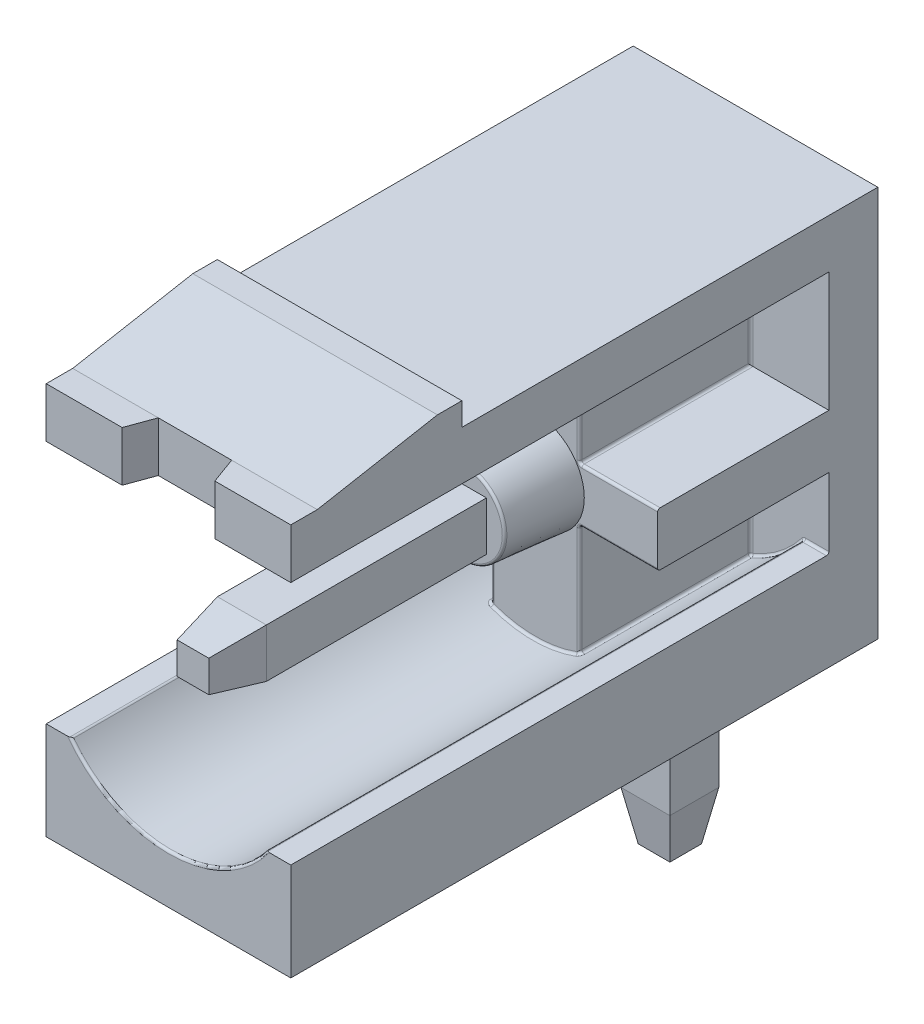
SolidWorks part; units mm, degrees
ref_plane "Спереди" through (0, 0, 0) normal (0, 0, 1) x (1, 0, 0)
ref_plane "Сверху" through (0, 0, 0) normal (0, 1, 0) x (1, 0, 0)
ref_plane "Справа" through (0, 0, 0) normal (1, 0, 0) x (0, 0, -1)
sketch "Эскиз1" plane through (0, 0, 0) normal (0, 0, 1) x (1, 0, 0)
  line L1 (-2.5, 0) -> (2.5, 0)
  line L2 (-2.5, 0) -> (-2.5, 8)
  line L3 (-2.5, 8) -> (2.5, 8)
  line L4 (2.5, 0) -> (2.5, 8)
extrude "Вытянуть1" add sketch "Эскиз1" along normal blind 12
sketch "Эскиз2" plane through (0, 0, 12) normal (0, 0, 1) x (1, 0, 0)
  line L0 (-2.5, 8) -> (-2.5, 0) construction
  line L1 (-2.5, 7) -> (2.5, 7)
  line L2 (-2.5, 7) -> (-2.5, 2)
  line L3 (-2.5, 2) -> (2.5, 2)
  line L4 (2.5, 7) -> (2.5, 2)
  line L5 (2.5, 0) -> (2.5, 8) construction
  dimension "D1" = 1
  dimension "D2" = 2
extrude "Вытянуть2" cut sketch "Эскиз2" against normal blind 11
sketch "Эскиз5" plane through (0, 0, 12) normal (0, 0, 1) x (1, 0, 0)
  line L0 (-2.5, 2) -> (-2, 2) construction
  line L1 (-2.5, 2) -> (2.5, 2) construction
  line L2 (2.5, 2) -> (2, 2) construction
  line L3 (0, 0) -> (0, 1) construction
  line L4 (-2.5, 0) -> (2.5, 0) construction
  circle A0 centre (0, 3.5) radius 2.5
extrude "Вытянуть3" cut sketch "Эскиз5" against normal blind 11
sketch "Эскиз6" plane through (0, 0, 12) normal (0, 0, 1) x (1, 0, 0)
  line L1 (0.5, 4.5) -> (-0.5, 4.5)
  line L2 (0.5, 4.5) -> (0.5, 3.5)
  line L3 (0.5, 3.5) -> (-0.5, 3.5)
  line L4 (-0.5, 4.5) -> (-0.5, 3.5)
  line L5 (0.5, 4.5) -> (-0.5, 3.5) construction
  line L6 (0.5, 3.5) -> (-0.5, 4.5) construction
  point P0 (0, 4)
  dimension "D1" = 1
  dimension "D2" = 1
sketch "Эскиз9" plane through (0, 0, 0) normal (0, -1, 0) x (1, 0, 0)
  line L0 (-2.5, 1.75) -> (2.5, 1.75) construction
  line L1 (-2.5, 12) -> (-2.5, 0) construction
  line L2 (2.5, 12) -> (2.5, 0) construction
  line L4 (-0.5, 2.25) -> (0.5, 2.25)
  line L5 (-0.5, 2.25) -> (-0.5, 1.25)
  line L6 (-0.5, 1.25) -> (0.5, 1.25)
  line L7 (0.5, 2.25) -> (0.5, 1.25)
  line L8 (-0.5, 2.25) -> (0.5, 1.25) construction
  line L9 (-0.5, 1.25) -> (0.5, 2.25) construction
  point P2 (0, 1.75)
  dimension "D1" = 1.75
sketch "Эскиз13" plane through (0, 0, 1) normal (0, 0, 1) x (1, 0, 0)
  line L0 (2.5, 7) -> (-2.5, 7) construction
  line L1 (-0.9, 1) -> (0.9, 1)
  line L2 (-0.9, 1) -> (-0.9, 7)
  line L3 (-0.9, 7) -> (0.9, 7)
  line L4 (0.9, 1) -> (0.9, 7)
  line L5 (-0.9, 1) -> (0.9, 7) construction
  line L6 (-0.9, 7) -> (0.9, 1) construction
  line L7 (2.5, 2) -> (2.5, 7) construction
  line L8 (-2.5, 4.55) -> (2.5, 4.55)
  line L9 (-2.5, 4.55) -> (-2.5, 3.45)
  line L10 (-2.5, 3.45) -> (2.5, 3.45)
  line L11 (2.5, 4.55) -> (2.5, 3.45)
  line L12 (-2.5, 4.55) -> (2.5, 3.45) construction
  line L13 (-2.5, 3.45) -> (2.5, 4.55) construction
  point P0 (0, 4)
  point P7 (0, 4)
  line M1 (2.5, 2) -> (2.5, 7)
  line M2 (2.5, 7) -> (-2.5, 7)
  line M3 (-2.5, 7) -> (-2.5, 2)
  arc M5 (-2, 2) -> (2, 2) centre (0, 3.5) ccw
  dimension "D1" = 1.1
  dimension "D2" = 1.8
extrude "Вытянуть13" add sketch "Эскиз13" along normal blind 3.5 contours L2 L10 L4 L8 | L2 L8 L4 M2 | L10 L2 L8 M3 | L10 L2 L4 M5 | L4 L10 L8 M1 region at (0, 2.252, 1) region at (-1.7, 4, 1) region at (0, 4, 1) region at (1.7, 4, 1) region at (0, 5.775, 1)
sketch "Эскиз14" plane through (0, 0, 4.5) normal (0, 0, 1) x (1, 0, 0)
  circle A0 centre (0, 4) radius 1
extrude "Вытянуть14" add sketch "Эскиз14" along normal blind 1.5
chamfer "Фаска1" distance 1.5 angle 5 1 edges at (1, 4, 6) first distance on face at (1, 4, 6)
sketch "Эскиз15" plane through (2.5, 0, 0) normal (1, 0, 0) x (0, 0, -1)
  line L0 (-12, 8) -> (-8.5024, 8)
  line L1 (-12, 8) -> (0, 8) construction
  line L2 (-8.5024, 8) -> (-8.5024, 8.4712)
  line L3 (-8.5024, 8.4712) -> (-9.0026, 8.4712)
  line L4 (-9.0026, 8.4712) -> (-11.4588, 8.0219)
  line L5 (-11.4588, 8.0219) -> (-12, 8.0219)
  line L6 (-12, 8.0219) -> (-12, 8)
extrude "Вытянуть15" add sketch "Эскиз15" against normal blind 5
sketch "Эскиз16" plane through (0, 8.0219, 0) normal (0, 1, 0) x (1, 0, 0)
  line L0 (0.75, -11.4588) -> (-0.75, -11.4588)
  line L1 (-2.5, -11.4588) -> (2.5, -11.4588) construction
  line L2 (-0.75, -11.4588) -> (-0.947, -12)
  line L3 (-2.5, -12) -> (2.5, -12) construction
  line L4 (0.75, -11.4588) -> (0.947, -12)
  line L5 (0.947, -12) -> (-0.947, -12)
  dimension "D1" = 1.75
  dimension "D2" = 1.75
extrude "Вытянуть16" cut sketch "Эскиз16" against normal up to next
sketch "Эскиз17" plane through (0, 0, 0) normal (0, 0, -1) x (-1, 0, 0)
  line L0 (2.5, 0) -> (-2.5, 0) construction
  line L1 (-0.6, 0) -> (0.6, 0)
  line L2 (-0.6, 0) -> (-0.6, 5)
  line L3 (-0.6, 5) -> (0.6, 5)
  line L4 (0.6, 0) -> (0.6, 5)
  dimension "D1" = 3
  dimension "D2" = 1.2
  dimension "D3" = 1.9
extrude "Вытянуть17" cut sketch "Эскиз17" against normal blind 2.25
sketch "Эскиз18" plane through (0, 0, 0) normal (0, 0, -1) x (-1, 0, 0)
  line L0 (-0.6, 0) -> (-2.5, 0) construction
  line L1 (-1.75, 0) -> (1.75, 0)
  line L2 (-1.75, 0) -> (-1.75, 6)
  line L3 (-1.75, 6) -> (1.75, 6)
  line L4 (1.75, 0) -> (1.75, 6)
  dimension "D1" = 0.75
  dimension "D2" = 3.5
  dimension "D3" = 2
extrude "Вытянуть18" cut sketch "Эскиз18" against normal blind 0.1
extrude "Вытянуть19" add sketch "Эскиз6" against normal up to body separate body
sketch "Эскиз19" plane through (0, 0, 12) normal (0, 0, 1) x (1, 0, 0)
  line L1 (-0.5, 4.5) -> (0.5, 4.5)
  line L2 (-0.5, 4.5) -> (-0.5, 3.5)
  line L3 (-0.5, 3.5) -> (0.5, 3.5)
  line L4 (0.5, 4.5) -> (0.5, 3.5)
extrude "Вытянуть20" cut sketch "Эскиз19" against normal blind 0.5
extrude "Вытянуть22" add sketch "Эскиз9" against normal up to body and the other way blind 4 separate body
chamfer "Фаска2" distance 1 angle 10 4 edges at (0, 4.5, 11.5) (0.5, 4, 11.5) (0, 3.5, 11.5) (-0.5, 4, 11.5) first distance on face at (0, 4.5, 8.75) first distance on face at (0.5, 4, 8.75) first distance on face at (0, 3.5, 8.75) first distance on face at (-0.5, 4, 8.75)
chamfer "Фаска3" distance 1 angle 10 4 edges at (0, -4, 1.25) (-0.5, -4, 1.75) (0, -4, 2.25) (0.5, -4, 1.75) first distance on face at (0, 0.5, 1.25) first distance on face at (-0.5, 0.5, 1.75) first distance on face at (0, 0.5, 2.25) first distance on face at (0.5, 0.5, 1.75)
fillet "Скругление3" radius 0.05 30 edges at (1.7, 3.45, 4.5) (1.7, 4.55, 4.5) (0, 7, 4.5) (-1.7, 4.55, 4.5) (-1.7, 3.45, 4.5) (2.25, 2, 1) (-2.25, 2, 1) (0.8688, 4, 6) (0.9, 2.3088, 4.5) (0.9, 3.45, 2.75) (0.9, 2.3088, 1) (0.9, 4.55, 2.75) (0.9, 5.775, 4.5) (0.9, 7, 2.75) (0.9, 5.775, 1) (-0.9, 7, 2.75) (-0.9, 5.775, 4.5) (-0.9, 4.55, 2.75) (-0.9, 5.775, 1) (-0.9, 3.45, 2.75) (-0.9, 2.3088, 4.5) (-0.9, 2.3088, 1) (0.9, 1.1676, 2.75) (1.5085, 1.5064, 1) (2, 2, 6.5) (0, 1, 12) (-2, 2, 6.5) (-1.5085, 1.5064, 1) (-0.9, 1.1676, 2.75) (0, 1, 4.5)
